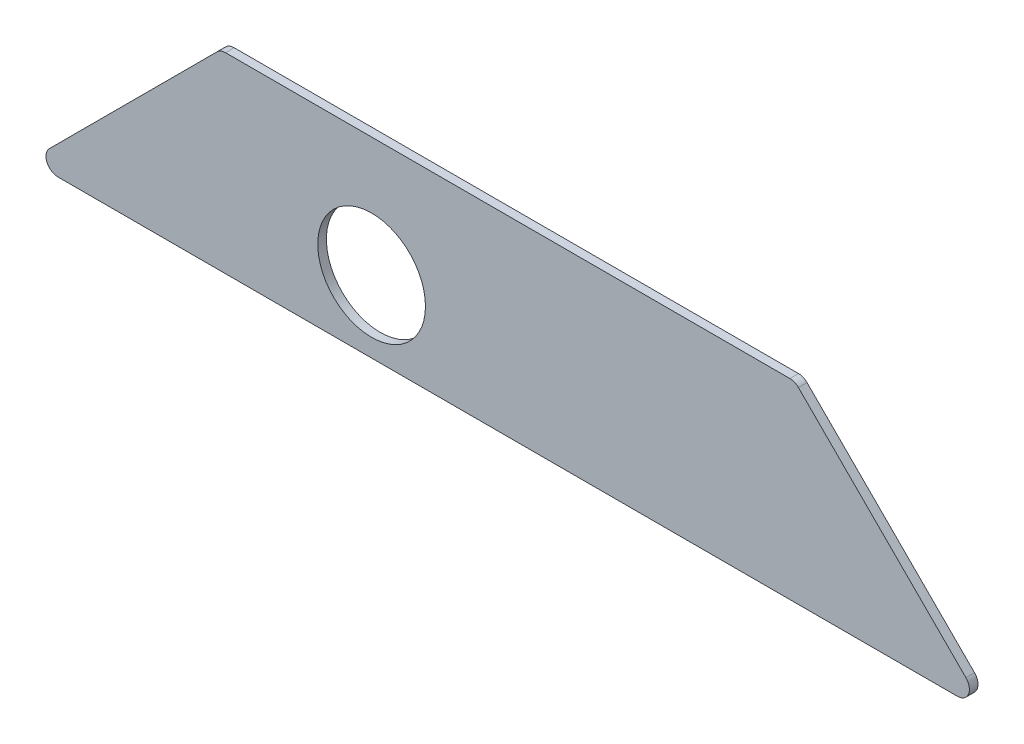
SolidWorks part; units mm, degrees
material "6061-T6 (SS)"
ref_plane "Front Plane" through (0, 0, 0) normal (0, 0, 1) x (1, 0, 0)
ref_plane "Top Plane" through (0, 0, 0) normal (0, 1, 0) x (1, 0, 0)
ref_plane "Right Plane" through (0, 0, 0) normal (1, 0, 0) x (0, 0, -1)
sketch "Sketch1" plane through (0, 0, 0) normal (0, 0, 1) x (1, 0, 0)
  line L0 (-76.2, 29.1622) -> (-127, -21.6378)
  line L1 (-76.2, 29.1622) -> (76.2, 29.1622)
  line L2 (-127, -21.6378) -> (127, -21.6378)
  line L3 (127, -21.6378) -> (76.2, 29.1622)
  point P0 (0, 0)
  point P1 (0, -21.6378)
  dimension "D1" = 135
  dimension "D2" = 254
  dimension "D3" = 50.8
  dimension "D4" = 135
extrude "Boss-Extrude1" add sketch "Sketch1" along normal mid plane 2.286
sketch "Sketch2" plane through (0, 0, 1.143) normal (0, 0, 1) x (1, 0, 0)
  line L0 (-127, -21.6378) -> (127, -21.6378) construction
  line L3 (-76.2, 29.1622) -> (-127, -21.6378) construction
  circle A0 centre (-36.108, -2.5878) radius 14.2875
  dimension "D1" = 19.05
  dimension "D2" = 28.575
  dimension "D3" = 50.8
extrude "Cut-Extrude1" cut sketch "Sketch2" against normal through all
fillet "Fillet1" radius 3.175 4 edges at (-127, -21.6378, 0) (-76.2, 29.1622, 0) (127, -21.6378, 0) (76.2, 29.1622, 0)
